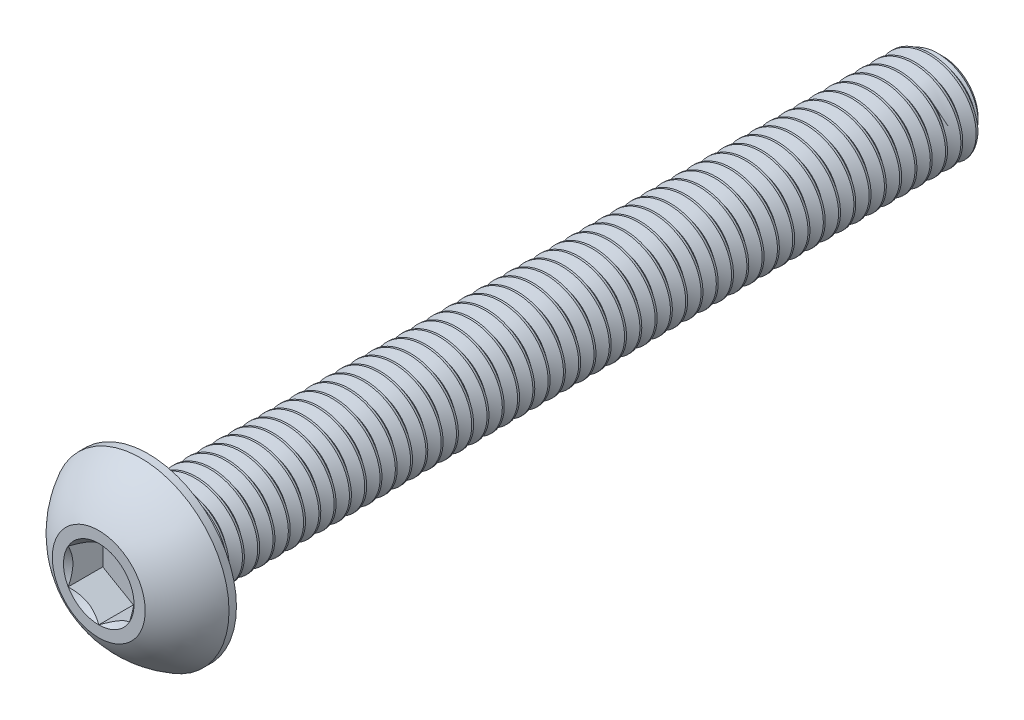
SolidWorks part; units mm, degrees
material "AISI 304"
ref_plane "Front" through (0, 0, 0) normal (0, 0, 1) x (1, 0, 0)
ref_plane "Top" through (0, 0, 0) normal (0, 1, 0) x (1, 0, 0)
ref_plane "Right" through (0, 0, 0) normal (1, 0, 0) x (0, 0, -1)
sketch "Sketch1" plane through (0, 0, 0) normal (1, 0, 0) x (0, 0, -1)
  line L2 (2.5654, 2.413) -> (43.8404, 2.413)
  line L3 (43.8404, 2.413) -> (43.8404, 0)
  line L4 (43.8404, 0) -> (2.5654, 0)
  line L6 (2.1806, 4.5847) -> (2.5654, 4.5847) construction
  line L7 (43.8404, 2.413) -> (43.8404, -2.413) construction
  line L8 (0, 0) -> (2.5654, 0) construction
  line L9 (2.5654, 4.5847) -> (2.5654, -4.5847) construction
  line L11 (2.5654, 2.413) -> (2.5654, 0)
  line L13 (0, 1.5875) -> (0, -1.5875) construction
  line L14 (0, 1.5875) -> (0, 2.413) construction
  arc A3 (0, 2.413) -> (2.1806, 4.5847) centre (4.5749, 0) cw construction
  dimension "D1" = 0.3848
  dimension "Head Ht" = 2.5654
  dimension "Head Dia" = 9.1694
  dimension "Dia" = 4.826
  dimension "Lg" = 41.275
  dimension "Hex" = 3.175
revolve "Revolve1" add sketch "Sketch1" angle 360 mid plane about L4
sketch "Sketch3" plane through (0, 0, -43.8404) normal (0, 0, -1) x (-1, 0, 0)
  circle A0 centre (0, 0) radius 2.413
curve "Helix/Spiral1" pitch 0.7937 height 42.0688 turns 53
sketch "Sketch2" plane through (0, 0, 0) normal (1, 0, 0) x (0, 0, -1)
  line L0 (43.8404, 2.413) -> (44.5349, 2.413)
  line L1 (44.5349, 2.413) -> (44.2373, 1.8974)
  line L2 (44.2373, 1.8974) -> (44.1381, 1.8974)
  line L3 (44.1381, 1.8974) -> (43.8404, 2.413)
  line L4 (43.9892, 2.1552) -> (44.3861, 2.1552) construction
  dimension "D1" = 60
  dimension "D2" = 0.0992
  dimension "D3" = 0.3969
chamfer "Chamfer1" distance 0.5953 angle 45 1 edges at (0, 2.413, -43.8404)
sweep "Cut-Sweep1" cut profiles "Sketch2" path "Helix/Spiral1"
sketch "Sketch7" plane through (0, 0, 0) normal (1, 0, 0) x (0, 0, -1)
  line L6 (2.1806, 4.5847) -> (2.5654, 4.5847) construction
  line L8 (0, 0) -> (2.5654, 0) construction
  line L11 (2.5654, 4.5847) -> (2.5654, -4.5847) construction
  line L12 (2.1806, 4.5847) -> (2.5654, 4.5847)
  line L13 (0, 0) -> (2.5654, 0)
  line L14 (0, 1.5875) -> (0, -1.5875) construction
  line L15 (2.5654, 4.5847) -> (2.5654, 0)
  line L16 (0, 2.413) -> (0, 0)
  arc A2 (2.1806, 4.5847) -> (0, 2.413) centre (4.5749, 0) ccw construction
  arc A3 (2.1806, 4.5847) -> (0, 2.413) centre (4.5749, 0) ccw
revolve "Revolve2" add sketch "Sketch7" angle 360 mid plane about L13
sketch "Sketch5" plane through (0, 0, 0) normal (0, 0, 1) x (1, 0, 0)
  line L1 (1.5875, -0.9165) -> (1.5875, 0.9165)
  line L2 (1.5875, 0.9165) -> (0, 1.8331)
  line L3 (0, 1.8331) -> (-1.5875, 0.9165)
  line L4 (-1.5875, 0.9165) -> (-1.5875, -0.9165)
  line L5 (-1.5875, -0.9165) -> (0, -1.8331)
  line L6 (0, -1.8331) -> (1.5875, -0.9165)
  circle A0 centre (0, 0) radius 1.5875 construction
extrude "Cut-Extrude2" cut sketch "Sketch5" against normal blind 1.7958
sketch "Sketch6" plane through (0, 0, 0) normal (0, 0, 1) x (1, 0, 0)
  circle A0 centre (0, 0) radius 1.8331
extrude "Cut-Extrude3" cut sketch "Sketch6" against normal blind 1.7958 draft 45
sketch "Sketch9" [suppressed] plane through (0, 0, -2.5654) normal (0, 0, 1) x (1, 0, 0)
  circle A2 centre (0, 0) radius 2.413
extrude "Boss-Extrude2" [suppressed] add sketch "Sketch9" against normal offset from surface (9.525 mm away) 31.75
sketch "Sketch10" plane through (0, 0, 0) normal (1, 0, 0) x (0, 0, -1)
  line L0 (43.8404, 2.413) -> (43.8404, -2.413) construction
  point P0 (42.6498, -2.413)
  dimension "D1" = 1.1906
equation "\"D3@Helix/Spiral1\" = \"Lg@Sketch1\" + \"D4@Helix/Spiral1\""
equation "\"D2@Sketch2\" = \"D4@Helix/Spiral1\" * .125"
equation "\"D3@Sketch2\" = \"D4@Helix/Spiral1\" * .5"
equation "\"D1@Chamfer1\" = \"D4@Helix/Spiral1\" * .75"
equation "\"D1@Cut-Extrude2\" = \"Head Ht@Sketch1\" * .7"
equation "\"D1@Sketch1\" = \"Head Ht@Sketch1\" * .15"
equation "\"D1@Sketch10\" = \"D4@Helix/Spiral1\" * 1.5"
equation "\"D1@Cut-Extrude3\" = \"D1@Cut-Extrude2\""
